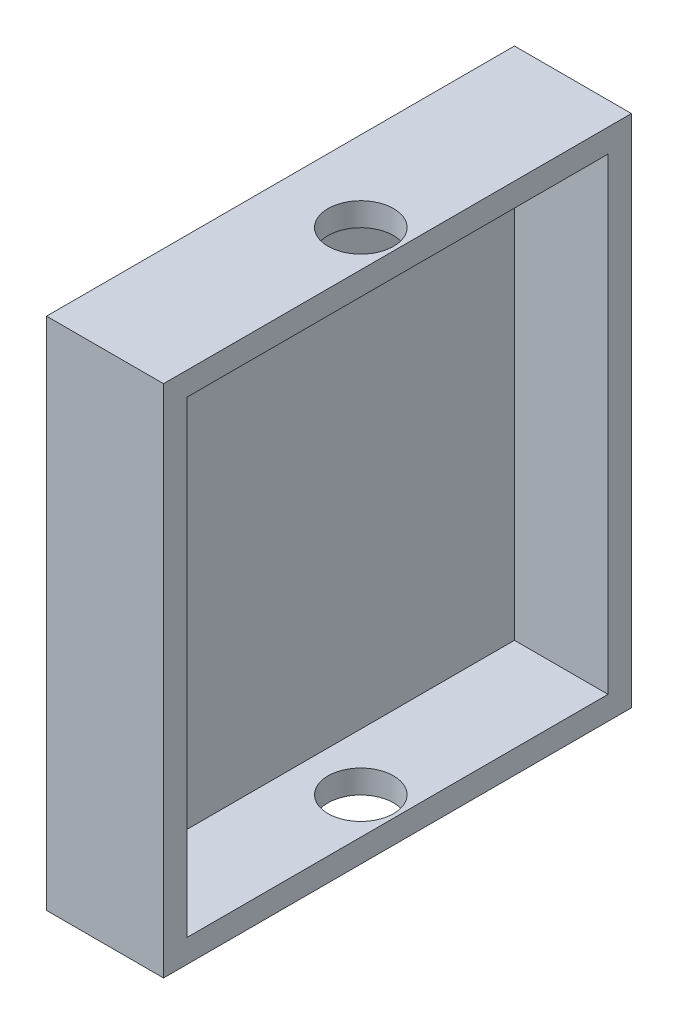
SolidWorks part; units mm, degrees
ref_plane "Front Plane" through (0, 0, 0) normal (0, 0, 1) x (1, 0, 0)
ref_plane "Top Plane" through (0, 0, 0) normal (0, 1, 0) x (1, 0, 0)
ref_plane "Right Plane" through (0, 0, 0) normal (1, 0, 0) x (0, 0, -1)
sketch "Sketch2" plane through (0, 0, 0) normal (1, 0, 0) x (0, 0, -1)
  line L1 (-50, -55) -> (50, -55)
  line L2 (-50, -55) -> (-50, 55)
  line L3 (-50, 55) -> (50, 55)
  line L4 (50, -55) -> (50, 55)
  line L5 (-50, -55) -> (50, 55) construction
  line L6 (-50, 55) -> (50, -55) construction
  line L7 (-45, -50) -> (45, -50)
  line L8 (-45, -50) -> (-45, 50)
  line L9 (-45, 50) -> (45, 50)
  line L10 (45, -50) -> (45, 50)
  line L11 (-45, -50) -> (45, 50) construction
  line L12 (-45, 50) -> (45, -50) construction
  point P0 (0, 0)
  point P6 (0, 0)
  dimension "D1" = 100
  dimension "D2" = 110
  dimension "D3" = 5
  dimension "D4" = 5
extrude "Boss-Extrude1" add sketch "Sketch2" along normal blind 5 contours L7 L10 L9 L8 | L1 L4 L3 L2 L10 L7 L8 L9 | L8 L7 L10 L9 | L2 L1 L4 L3 region at (0, 0, 48.5134) region at (0, 0, 0)
extrude "Boss-Extrude2" add sketch "Sketch2<3>" along normal blind 25
sketch "Sketch2<3>" plane through (0, 0, 0) normal (1, 0, 0) x (0, 0, -1) same geometry as "Sketch2"
sketch "Sketch3" plane through (0, -55, 0) normal (0, -1, 0) x (1, 0, 0)
  line L0 (0, 50) -> (0, -50) construction
  line L1 (5, -45) -> (5, 45) construction
  circle A0 centre (17.16, 0) radius 7
  point P4 (0, 0)
  point P5 (0, 0)
  dimension "D2" = 14
  dimension "D1" = 12.16
extrude "Cut-Extrude1" cut sketch "Sketch3" against normal through all
